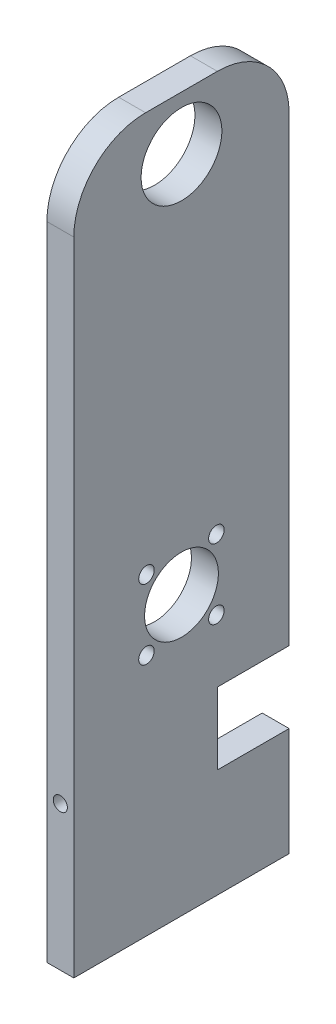
SolidWorks part; units mm, degrees
ref_plane "Front Plane" through (0, 0, 0) normal (0, 0, 1) x (1, 0, 0)
ref_plane "Top Plane" through (0, 0, 0) normal (0, 1, 0) x (1, 0, 0)
ref_plane "Right Plane" through (0, 0, 0) normal (1, 0, 0) x (0, 0, -1)
sketch "Sketch1" plane through (0, 0, 0) normal (0, 1, 0) x (1, 0, 0)
  line L1 (-4.7625, 38.1) -> (4.7625, 38.1)
  line L2 (-4.7625, 38.1) -> (-4.7625, -38.1)
  line L3 (-4.7625, -38.1) -> (4.7625, -38.1)
  line L4 (4.7625, 38.1) -> (4.7625, -38.1)
  line L5 (-4.7625, 38.1) -> (4.7625, -38.1) construction
  line L6 (-4.7625, -38.1) -> (4.7625, 38.1) construction
  point P0 (0, 0)
  dimension "D1" = 76.2
  dimension "D2" = 9.525
extrude "Boss-Extrude1" add sketch "Sketch1" along normal mid plane 252.476
sketch "Sketch3" plane through (-4.7625, 0, 0) normal (-1, 0, 0) x (0, 0, 1)
  line L0 (-45.1772, -15.4437) -> (44.4211, -15.4437) construction
  line L1 (-45.1772, -40.1878) -> (44.4211, -40.1878) construction
  line L2 (-38.1, 126.238) -> (38.1, 126.238) construction
  line L3 (-45.1772, -27.813) -> (44.4211, -27.813) construction
  line L4 (-12.3658, -8.7664) -> (-12.3658, -58.1325) construction
  line L5 (12.3748, -8.7664) -> (12.3748, -58.1325) construction
  line L6 (0, -8.7664) -> (0, -58.1325) construction
  circle A0 centre (0, 107.188) radius 14.2875
  circle A1 centre (-12.3658, -15.4437) radius 2.75
  circle A2 centre (12.3748, -15.4437) radius 2.75
  circle A3 centre (-12.3658, -40.1878) radius 2.75
  circle A4 centre (12.3748, -40.1878) radius 2.75
  circle A5 centre (0, -27.813) radius 13.0556
  point P12 (-38.1, 126.238)
  dimension "D1" = 28.575
  dimension "D2" = 19.05
  dimension "D3" = 12.3658
  dimension "D4" = 12.3748
  dimension "D7" = 26.1112
  dimension "D8" = 5.5
  dimension "D5" = 12.3693
  dimension "D6" = 12.3748
  dimension "D9" = 24.7406
extrude "Cut-Extrude2" cut sketch "Sketch3" against normal blind 45.974
fillet "Fillet1" radius 25.4 2 edges at (0, 126.238, 38.1) (0, 126.238, -38.1)
sketch "Sketch4" plane through (-4.7625, 0, 0) normal (-1, 0, 0) x (0, 0, 1)
  line L0 (-38.1, 100.838) -> (-38.1, -126.238) construction
  circle A0 centre (-1.5, 11.3124) radius 2.5
  circle A1 centre (-1.5, -54.6876) radius 2.5
  circle A2 centre (0, -21.6876) radius 7.9248
  dimension "D4" = 36.6
  dimension "D5" = 5
  dimension "D2" = 15.8496
  dimension "D1" = 66
  dimension "D3" = 33
  dimension "D6" = 1.5
  dimension "D7" = 1.5
  dimension "D8" = 38.1
extrude "Cut-Extrude3" [suppressed] cut sketch "Sketch4" against normal through all
sketch "Sketch5" plane through (-4.7625, 0, 0) normal (-1, 0, 0) x (0, 0, 1)
  line L0 (38.1, -126.238) -> (-38.1, -126.238) construction
  line L1 (-38.1, 100.838) -> (-38.1, -126.238) construction
  line L2 (-38.1, -62.484) -> (-12.7, -62.484)
  line L3 (-38.1, -62.484) -> (-38.1, -87.884)
  line L4 (-38.1, -87.884) -> (-12.7, -87.884)
  line L6 (-12.7, -62.484) -> (-12.7, -87.884)
  dimension "D1" = 38.354
  dimension "D2" = 25.4
extrude "Cut-Extrude4" cut sketch "Sketch5" against normal through all contours L2 L6 L4 L3
hole_wizard "Tap Drill for M6x1.0 Tap1" positions "Sketch7" profile "Sketch6" hole size "M6x1.0" standard "ANSI Metric" end condition through all
sketch "Sketch7" plane through (0, 0, -12.7) normal (0, 0, -1) x (-1, 0, 0)
  line L0 (-4.7625, -62.484) -> (4.7625, -62.484) construction
  point P0 (0, -75.184)
  dimension "D1" = 12.7
sketch "Sketch6" plane through (0, -75.184, -12.7) normal (1, 0, 0) x (0, 1, 0)
  line L0 (0, 0) -> (0, 50.8)
  line L1 (0, 50.8) -> (2.5, 50.8)
  line L2 (2.5, 50.8) -> (2.5, 0)
  line L5 (2.5, 0) -> (0, 0)
  line L11 (0, -6.35) -> (0, 107.95) construction
  dimension "Thru Hole Dia." = 5
  dimension "Thru Hole Depth" = 50.8
